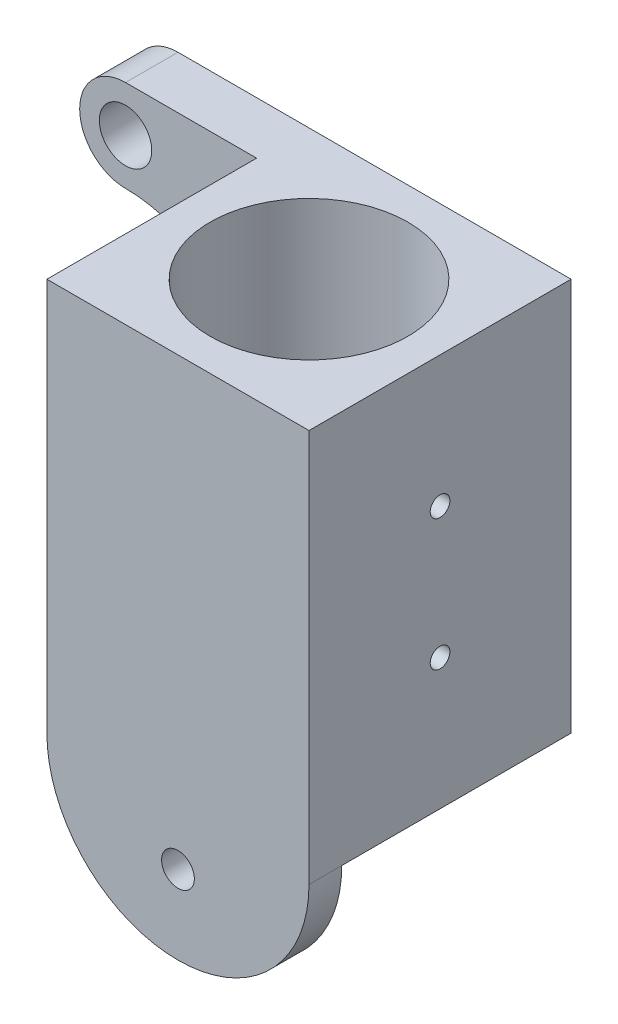
SolidWorks part; units mm, degrees
ref_plane "前基準面" through (0, 0, 0) normal (0, 0, 1) x (1, 0, 0)
ref_plane "上基準面" through (0, 0, 0) normal (0, 1, 0) x (1, 0, 0)
ref_plane "右基準面" through (0, 0, 0) normal (1, 0, 0) x (0, 0, -1)
sketch "草圖1" plane through (0, 0, 0) normal (0, 1, 0) x (1, 0, 0)
  line L1 (-20, 20) -> (20, 20)
  line L2 (-20, 20) -> (-20, -20)
  line L3 (-20, -20) -> (20, -20)
  line L4 (20, 20) -> (20, -20)
  line L5 (-20, 20) -> (20, -20) construction
  line L6 (-20, -20) -> (20, 20) construction
  dimension "D2" = 40
extrude "填料-伸長1" add sketch "草圖1" along normal blind 60
sketch "草圖2" plane through (0, 60, 0) normal (0, 1, 0) x (1, 0, 0)
  circle A0 centre (0, 0) radius 15.1
  dimension "D1" = 30.2
extrude "除料-伸長1" cut sketch "草圖2" against normal blind 50
sketch "草圖3" plane through (0, 0, 20) normal (0, 0, 1) x (1, 0, 0)
  line L0 (-20, 0) -> (20, 0)
  arc A0 (-20, 0) -> (20, 0) centre (0, 0) ccw
  circle A1 centre (0, -8) radius 2.5
  dimension "D1" = 5
  dimension "D2" = 8
extrude "填料-伸長2" add sketch "草圖3" against normal blind 5
sketch "草圖4" plane through (20, 0, 0) normal (1, 0, 0) x (0, 0, -1)
  circle A0 centre (0, 20) radius 1.5
  dimension "D1" = 3
  dimension "D2" = 20
extrude "除料-伸長2" cut sketch "草圖4" against normal through all
pattern_linear "直線複製排列1" count 2 spacing 20 along (0, 1, 0) of "除料-伸長2"
sketch "草圖5" plane through (-20, 0, 0) normal (-1, 0, 0) x (0, 0, 1)
  line L1 (-20, 60) -> (-12, 60)
  line L2 (-20, 60) -> (-20, 46)
  line L3 (-20, 46) -> (-12, 46)
  line L4 (-12, 60) -> (-12, 46)
  dimension "D1" = 8
  dimension "D2" = 14
extrude "填料-伸長3" add sketch "草圖5" along normal blind 27
fillet "圓角1" radius 7 2 edges at (-47, 46, -16) (-47, 60, -16)
sketch "草圖6" plane through (0, 0, -20) normal (0, 0, -1) x (-1, 0, 0)
  circle A0 centre (40, 53) radius 4
  dimension "D1" = 8
extrude "除料-伸長3" cut sketch "草圖6" against normal up to next
fillet "圓角2" radius 20 1 edges at (-20, 46, -16)
